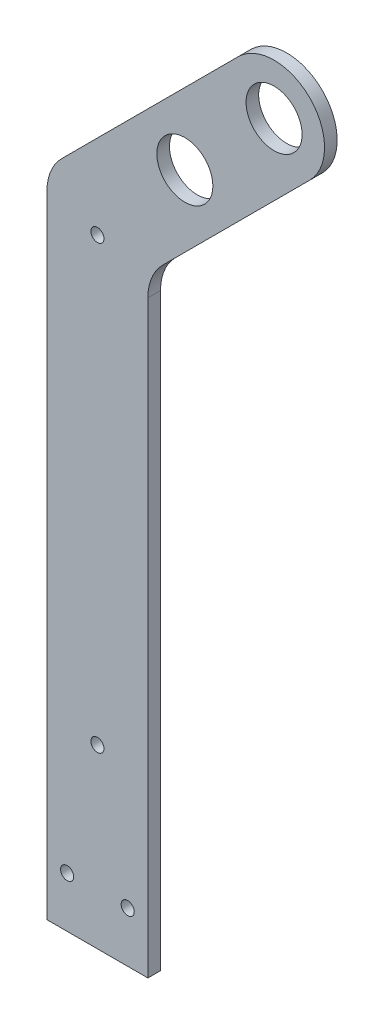
SolidWorks part; units mm, degrees
material "6061 合金"
ref_plane "前视基准面" through (0, 0, 0) normal (0, 0, 1) x (1, 0, 0)
ref_plane "上视基准面" through (0, 0, 0) normal (0, 1, 0) x (1, 0, 0)
ref_plane "右视基准面" through (0, 0, 0) normal (1, 0, 0) x (0, 0, -1)
other "Configuration Table"
sketch "草图1" plane through (0, 0, 0) normal (0, 0, 1) x (1, 0, 0)
  circle A0 centre (0, 0) radius 20
  circle A1 centre (0, 0) radius 11.1
  dimension "D1" = 40
  dimension "D2" = 22.2
extrude "凸台-拉伸1" add sketch "草图1" along normal blind 60 contours A1 | A0 region at (0, 0, 0)
ref_plane "基准面1" through (0, 0, 30) normal (0, 0, 1) x (1, 0, 0)
sketch "草图2" plane through (0, 0, 30) normal (0, 0, 1) x (1, 0, 0)
  line L0 (0, 0) -> (-70, -70) construction
  line L1 (-70, -70) -> (-70, -320) construction
  line L2 (0, -57.3148) -> (0, 49.9409) construction
  line L3 (-56.8582, 0) -> (46.4003, 0) construction
  line L4 (-14.1421, 14.1421) -> (-90, -61.7157)
  line L5 (14.1421, -14.1421) -> (-50, -78.2843)
  line L6 (-90, -61.7157) -> (-90, -320)
  line L7 (-50, -78.2843) -> (-50, -320)
  line L8 (-90, -320) -> (-50, -320)
  circle A2 centre (0, 0) radius 20 construction
  arc A3 (-14.1421, 14.1421) -> (14.1421, -14.1421) centre (0, 0) ccw
  dimension "D1" = 45
  dimension "D2" = 250
  dimension "D3" = 70
  dimension "D4" = 40
  dimension "D5" = 40
extrude "凸台-拉伸2" add sketch "草图2" along normal mid plane 60 contours L7 L8 L6 L4 A3 L5
sketch "草图4" plane through (0, 0, 60) normal (0, 0, 1) x (1, 0, 0)
  line L0 (-90, -61.7157) -> (-90, -320) construction
  line L1 (-90, -290) -> (-50, -290)
  line L2 (-90, -290) -> (-90, -350)
  line L4 (-50, -290) -> (-50, -350)
  line L5 (-50, -78.2843) -> (-50, -320) construction
  line L6 (-90, -320) -> (-50, -320) construction
  arc A0 (-90, -350) -> (-50, -350) centre (-70, -350) ccw
  circle A1 centre (-70, -350) radius 11
  dimension "D3" = 22
  dimension "D1" = 30
  dimension "D2" = 30
extrude "凸台-拉伸3" add sketch "草图4" along normal blind 5
mirror "镜向1" about plane through (0, 0, 30) normal (0, 0, 1) of "凸台-拉伸3"
sketch "草图5" plane through (0, 0, 0) normal (0, 1, 0) x (1, 0, 0)
  line L0 (0, 0) -> (0, -78.0582) construction
ref_plane "基准面2" through (-70, 0, 0) normal (-1, 0, 0) x (0, 0, 1)
sketch "草图7" plane through (-70, 0, 0) normal (-1, 0, 0) x (0, 0, 1)
  line L0 (-34.1239, -350) -> (109.535, -350) construction
sketch "草图8" plane through (0, 0, 60) normal (0, 0, 1) x (1, 0, 0)
  line L0 (0, 0) -> (-70, -70) construction
  circle A0 centre (-35.3553, -35.3553) radius 11.1
  dimension "D1" = 22.2
  dimension "D2" = 50
extrude "切除-拉伸1" cut sketch "草图8" against normal blind 100
fillet "圆角4" radius 20 2 edges at (-90, -61.7157, 30) (-50, -78.2843, 30)
fillet "圆角1" [suppressed] radius 50
fillet "圆角2" [suppressed] radius 3
sketch "草图9" plane through (0, 0, 65) normal (0, 0, 1) x (1, 0, 0)
  circle A0 centre (-70, -350) radius 13
  dimension "D1" = 26
extrude "切除-拉伸2" [suppressed] cut sketch "草图9" against normal blind 0.75
sketch "草图10" plane through (0, 0, -5) normal (0, 0, -1) x (-1, 0, 0)
  circle A0 centre (70, -350) radius 13
  dimension "D1" = 26
extrude "切除-拉伸3" [suppressed] cut sketch "草图10" against normal blind 0.75 contours A0
sketch "草图11" plane through (-90, 0, 0) normal (-1, 0, 0) x (0, 0, 1)
  circle A0 centre (48.5, -118.9949) radius 2.75
  circle A1 centre (48.5, -183.9949) radius 2.75
  circle A2 centre (48.5, -248.9949) radius 2.75
  circle A3 centre (11.5, -248.9949) radius 2.75
  circle A4 centre (11.5, -183.9949) radius 2.75
  circle A5 centre (11.5, -118.9949) radius 2.75
  dimension "D1" = 5.5
extrude "切除-拉伸4" [suppressed] cut sketch "草图11" against normal through all contours A1 | A2 | A0 | A3 | A4 | A5
sketch "草图12" [suppressed] plane through (-90, 0, 0) normal (-1, 0, 0) x (0, 0, 1)
  line L0 (30, -62.0134) -> (30, -339.6946) construction
  line L1 (10, -128.9949) -> (50, -128.9949)
  line L2 (10, -128.9949) -> (10, -173.9949)
  line L3 (10, -173.9949) -> (50, -173.9949)
  line L4 (50, -128.9949) -> (50, -173.9949)
  line L5 (10, -193.9949) -> (50, -193.9949)
  line L6 (10, -193.9949) -> (10, -238.9949)
  line L7 (10, -238.9949) -> (50, -238.9949)
  line L8 (50, -193.9949) -> (50, -238.9949)
  line L9 (10, -258.9949) -> (50, -258.9949)
  line L10 (10, -258.9949) -> (10, -290)
  line L11 (10, -290) -> (50, -290)
  line L12 (50, -258.9949) -> (50, -290)
  line L13 (19.5, -173.9949) -> (40.5, -173.9949)
  line L14 (19.5, -173.9949) -> (19.5, -193.9949)
  line L15 (19.5, -193.9949) -> (40.5, -193.9949)
  line L16 (40.5, -173.9949) -> (40.5, -193.9949)
  line L17 (19.5, -238.9949) -> (40.5, -238.9949)
  line L18 (19.5, -238.9949) -> (19.5, -258.9949)
  line L19 (19.5, -258.9949) -> (40.5, -258.9949)
  line L20 (40.5, -238.9949) -> (40.5, -258.9949)
  line L21 (60, -82.4264) -> (60, -290) construction
  line L22 (0, -290) -> (0, -82.4264) construction
  line L23 (57, -320) -> (3, -320) construction
  circle A0 centre (48.5, -118.9949) radius 2.75 construction
  circle A1 centre (48.5, -183.9949) radius 2.75 construction
  circle A2 centre (48.5, -248.9949) radius 2.75 construction
  dimension "D1" = 10
  dimension "D2" = 10
  dimension "D3" = 10
  dimension "D4" = 8
  dimension "D5" = 10
  dimension "D6" = 10
  dimension "D7" = 10
  dimension "D8" = 30
extrude "减重" [suppressed] cut sketch "草图12" against normal through all contours L0 L1 L2 L3 | L15 L0 L17 L7 L8 L5 | L0 L5 L6 L7 | L19 L0 L11 L12 L9 | L0 L9 L10 L11 | L1 L0 L13 L3 L4
fillet "圆角3" [suppressed] radius 3
sketch "草图13" plane through (0, 0, 60) normal (0, 0, 1) x (1, 0, 0)
  circle A0 centre (0, 0) radius 13
  circle A1 centre (-35.3553, -35.3553) radius 13
  dimension "D1" = 26
  dimension "D2" = 26
extrude "切除-拉伸6" [suppressed] cut sketch "草图13" against normal blind 1.75
sketch "草图14" plane through (0, 0, 0) normal (0, 0, -1) x (-1, 0, 0)
  circle A0 centre (0, 0) radius 13
  circle A1 centre (35.3553, -35.3553) radius 13
  dimension "D1" = 26
  dimension "D2" = 26
extrude "切除-拉伸7" [suppressed] cut sketch "草图14" against normal blind 1.75
sketch "草图15" [suppressed] plane through (0, 0, 0) normal (0, 0, -1) x (-1, 0, 0)
  line L0 (0, 0) -> (70, -350) construction
  line L1 (56.2719, -67.2005) -> (60.1942, -86.8121) construction
  line L2 (70, -350) -> (204.3541, -323.1292) construction
  circle A0 centre (56.2719, -67.2005) radius 2.75
  circle A1 centre (75.2172, -73.6095) radius 2.75
  circle A2 centre (60.1942, -86.8121) radius 2.75
  dimension "D1" = 5.5
  dimension "D2" = 20
  dimension "D3" = 20
  dimension "D4" = 20
  dimension "D5" = 42
  dimension "D6" = 270
extrude "切除-拉伸8" [suppressed] cut sketch "草图15" against normal through all contours A2 | A0 | A1
ref_plane "小腿主干连杆面" through (0, 0, 0) normal (0.9806, -0.1961, 0) x (0, 0, -1)
ref_plane "小腿主干对称面" through (0, 0, 30) normal (0, 0, -1) x (-1, 0, 0)
sketch "草图16" plane through (0, 0, 60) normal (0, 0, 1) x (1, 0, 0)
  line L0 (0, 0) -> (-70, -350)
  line L1 (-35.3553, -35.3553) -> (0, 0)
sketch "草图17" plane through (0, 0, 60) normal (0, 0, 1) x (1, 0, 0)
  line L0 (0, 0) -> (-70, -350) construction
  line L1 (118.6974, 32.5948) -> (32.9122, -396.3312) construction
  line L2 (92.7764, -97.0102) -> (20.2919, -82.5133)
  line L3 (73.1648, -195.0683) -> (0.6803, -180.5713)
  circle A0 centre (20.2919, -82.5133) radius 46
  circle A1 centre (0.6803, -180.5713) radius 46
  dimension "D3" = 92
  dimension "D4" = 92
  dimension "D1" = 110
  dimension "D2" = 73.92
  dimension "D5" = 180
  dimension "D6" = 280
sketch "草图18" plane through (0, 0, 60) normal (0, 0, 1) x (1, 0, 0)
  line L1 (14.1421, -14.1421) -> (-44.1421, -72.4264) construction
  line L3 (14.1421, -14.1421) -> (-44.1421, -72.4264)
  line L4 (15.4873, -12.6548) -> (52.8188, -49.9864)
  line L5 (-50, -128.5133) -> (20.2919, -128.5133)
  line L10 (-90, -290) -> (-50, -290)
  line L11 (-50, -290) -> (-50, -86.5685)
  line L12 (-44.1421, -72.4264) -> (14.1421, -14.1421)
  line L13 (-14.1421, 14.1421) -> (-84.1421, -55.8579)
  line L14 (-90, -70) -> (-90, -290)
  line L16 (-50, -128.5133) -> (-50, -86.5685)
  line L17 (-44.1421, -72.4264) -> (14.1421, -14.1421)
  circle A0 centre (20.2919, -82.5133) radius 46 construction
  arc A1 (14.1421, -14.1421) -> (-14.1421, 14.1421) centre (0, 0) ccw construction
  arc A2 (14.1421, -14.1421) -> (-14.1421, 14.1421) centre (0, 0) ccw
  arc A3 (14.1421, -14.1421) -> (15.4873, -12.6548) centre (0, 0) ccw
  arc A4 (20.2919, -128.5133) -> (52.8188, -49.9864) centre (20.2919, -82.5133) ccw
  circle A5 centre (20.2919, -82.5133) radius 35
  arc A9 (-84.1421, -55.8579) -> (-90, -70) centre (-70, -70) ccw
  arc A10 (-84.1421, -55.8579) -> (-90, -70) centre (-70, -70) ccw
  arc A11 (-44.1421, -72.4264) -> (-50, -86.5685) centre (-30, -86.5685) ccw
  arc A12 (-44.1421, -72.4264) -> (-50, -86.5685) centre (-30, -86.5685) ccw
  line M14 (-50, -290) -> (-50, -86.5685)
  line M15 (-44.1421, -72.4264) -> (14.1421, -14.1421)
  arc M16 (14.1421, -14.1421) -> (-14.1421, 14.1421) centre (0, 0) ccw
  arc M22 (-50, -86.5685) -> (-44.1421, -72.4264) centre (-30, -86.5685) cw
  dimension "D2" = 70
  dimension "D1" = 0
extrude "凸台-拉伸4" add sketch "草图18" against normal blind 5 from offset 25 contours L5 A4 L4 A5 M16 M15 M22 M14 region at (16.0508, -14.5165, 60) offset against normal yes
sketch "草图19" plane through (0, 0, 0) normal (0, 0, -1) x (-1, 0, 0)
  line L0 (50, -86.5685) -> (50, -290) construction
  line L1 (50, -134.5713) -> (50, -226.5713)
  line L2 (-0.6803, -134.5713) -> (50, -134.5713)
  line L3 (-0.6803, -226.5713) -> (50, -226.5713)
  circle A0 centre (-0.6803, -180.5713) radius 46 construction
  arc A1 (-0.6803, -134.5713) -> (-0.6803, -226.5713) centre (-0.6803, -180.5713) ccw
  circle A2 centre (-0.6803, -180.5713) radius 35
  dimension "D1" = 70
extrude "凸台-拉伸5" add sketch "草图19" against normal blind 5 from offset 25 offset against normal yes
fillet "圆角5" radius 10 2 edges at (-50, -226.5713, 27.5) (-50, -128.5133, 32.5)
sketch "草图21" plane through (0, 0, 65) normal (0, 0, 1) x (1, 0, 0)
  line L0 (-70, -350) -> (-70, -6.9331) construction
  circle A0 centre (-70, -75) radius 2.6
  circle A1 centre (-70, -250) radius 2.6
  circle A2 centre (-58, -300) radius 2.6
  circle A3 centre (-82, -300) radius 2.6
  dimension "D1" = 5.2
  dimension "D2" = 12
  dimension "D3" = 50
  dimension "D4" = 100
  dimension "D5" = 175
extrude "切除-拉伸9" cut sketch "草图21" against normal through all both and the other way through all
sketch "草图22" plane through (-90, 0, 0) normal (-1, 0, 0) x (0, 0, 1)
  line L0 (-5, -350) -> (-5, -370) construction
  line L5 (-5, -377.8103) -> (55, -377.8103)
  line L6 (-5, -377.8103) -> (-5, 64.9179)
  line L7 (-5, 64.9179) -> (55, 64.9179)
  line L8 (55, -377.8103) -> (55, 64.9179)
  line L10 (65, -370) -> (60, -370)
  line L11 (65, -370) -> (65, 61.088)
  line L12 (65, 61.088) -> (60, 61.088)
  line L13 (60, -370) -> (60, 61.088)
  dimension "D1" = 5
  dimension "D2" = 5
extrude "切除-拉伸10" cut sketch "草图22" against normal through all both contours L8 L7 L6 L5 | L13 L12 L11 L10
